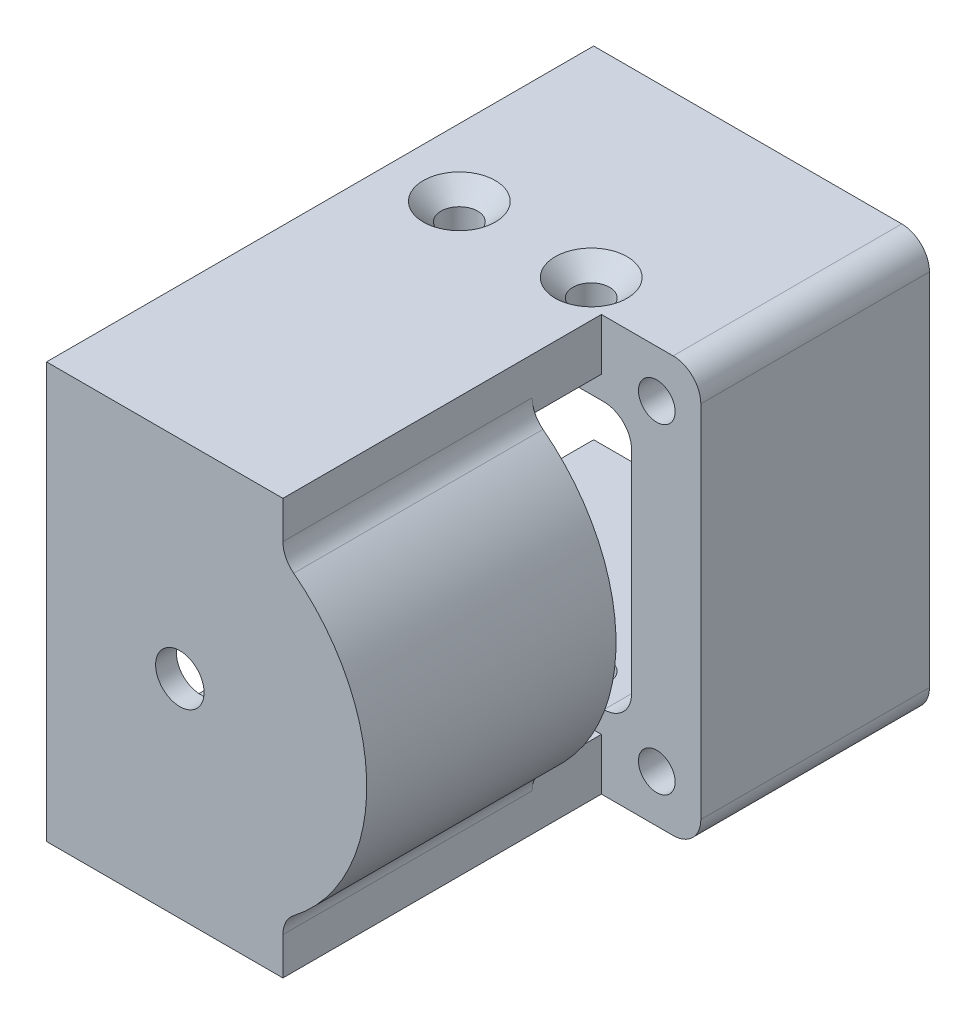
SolidWorks part; units mm, degrees
material "ABS"
ref_plane "Front Plane" through (0, 0, 0) normal (0, 0, 1) x (1, 0, 0)
ref_plane "Top Plane" through (0, 0, 0) normal (0, 1, 0) x (1, 0, 0)
ref_plane "Right Plane" through (0, 0, 0) normal (1, 0, 0) x (0, 0, -1)
sketch "Sketch1" plane through (0, 0, 0) normal (0, 0, 1) x (1, 0, 0)
  line L0 (-19.25, 19.25) -> (-19.25, 30)
  line L1 (-19.25, -19.25) -> (19.25, -19.25)
  line L3 (-19.25, 19.25) -> (19.25, 19.25)
  line L4 (19.25, -19.25) -> (19.25, 19.25)
  line L5 (-19.25, -19.25) -> (19.25, 19.25) construction
  line L6 (-19.25, 19.25) -> (19.25, -19.25) construction
  line L7 (-19.25, 30) -> (29.25, 30)
  line L8 (29.25, 30) -> (29.25, -30)
  line L9 (29.25, -30) -> (-19.25, -30)
  line L10 (-19.25, -30) -> (-19.25, -19.25)
  line L11 (0, 0) -> (19.25, 0) construction
  line L12 (19.25, 19.25) -> (29.25, 30) construction
  point P0 (0, 0)
  point P12 (22.8878, 23.1606)
  point P13 (22.8878, -23.1606)
  point P16 (24.25, 24.625)
  dimension "D1" = 38.5
  dimension "D2" = 38.5
  dimension "D3" = 60
  dimension "D4" = 10
  dimension "D5" = 2
extrude "Boss-Extrude1" add sketch "Sketch1" along normal mid plane 33.02
hole_wizard "M5 Clearance Hole1" positions "Sketch4" profile "Sketch5" hole size "M5" standard "ANSI Metric" end condition through all
sketch "Sketch4" plane through (0, 0, -16.51) normal (0, 0, -1) x (-1, 0, 0)
  point P4 (-22.8878, -23.1606)
  point P9 (-22.8878, 23.1606)
sketch "Sketch5" plane through (22.8878, -23.1606, -16.51) normal (1, 0, 0) x (0, 1, 0)
  line L0 (0, 0) -> (0, 33.02)
  line L1 (0, 33.02) -> (2.65, 33.02)
  line L2 (2.65, 33.02) -> (2.65, 0)
  line L5 (2.65, 0) -> (0, 0)
  line L11 (0, -6.35) -> (0, 107.95) construction
  dimension "Thru Hole Dia." = 5.3
  dimension "Thru Hole Depth" = 33.02
fillet "Fillet1" radius 4 4 edges at (29.25, -30, 0) (29.25, 30, 0) (19.25, -19.25, 0) (19.25, 19.25, 0)
sketch "Sketch6" plane through (0, 0, 16.51) normal (0, 0, 1) x (1, 0, 0)
  line L2 (-19.25, 22.5) -> (-19.25, 30)
  line L3 (-19.25, 30) -> (14.8878, 30)
  line L4 (25.25, 30) -> (-19.25, 30) construction
  line L5 (14.8878, 30) -> (14.8878, 22.5245)
  line L6 (22.8878, 27.7794) -> (18.8878, 25.47) construction
  line L7 (18.8878, 25.47) -> (18.8878, 20.8512) construction
  line L8 (18.8878, 20.8512) -> (22.8878, 18.5418) construction
  line L9 (22.8878, 18.5418) -> (26.8878, 20.8512) construction
  line L10 (26.8878, 20.8512) -> (26.8878, 25.47) construction
  line L11 (26.8878, 25.47) -> (22.8878, 27.7794) construction
  line L12 (0, 0) -> (19.25, 0) construction
  line L13 (19.25, 15.25) -> (19.25, -15.25) construction
  line L15 (-19.25, -22.5) -> (-19.25, -30)
  line L16 (-19.25, -30) -> (14.8878, -30)
  line L17 (14.8878, -30) -> (14.8878, -22.5245)
  line L18 (0, 22.5) -> (-19.25, 22.5)
  line L19 (0, -22.5) -> (-19.25, -22.5)
  arc A0 (0, -22.5) -> (0, 22.5) centre (0, 0) ccw
  circle A1 centre (22.8878, 23.1606) radius 4 construction
  arc A3 (14.8878, -22.5245) -> (14.8878, 22.5245) centre (0, 0) ccw
  dimension "D1" = 45
  dimension "D4" = 27
  dimension "D2" = 8
  dimension "D3" = 4
extrude "Boss-Extrude2" add sketch "Sketch6" along normal blind 43
sketch "Sketch7" plane through (29.25, 0, 0) normal (1, 0, 0) x (0, 0, -1)
  line L0 (-59.51, -22.5245) -> (-16.51, -22.5245) construction
  line L1 (-16.51, 22.5245) -> (-26.51, 22.5245)
  line L2 (-16.51, 22.5245) -> (-16.51, -22.5245)
  line L3 (-16.51, -22.5245) -> (-26.51, -22.5245)
  line L4 (-26.51, 22.5245) -> (-26.51, -22.5245)
  point P7 (0, 0)
  dimension "D1" = 10
extrude "Cut-Extrude1" cut sketch "Sketch7" against normal through all both and the other way through all
fillet "Fillet2" radius 4 2 edges at (14.8878, -22.5245, 43.01) (14.8878, 22.5245, 43.01)
sketch "Sketch8" plane through (0, 0, 59.51) normal (0, 0, 1) x (1, 0, 0)
  line L0 (-19.25, 22.5) -> (-19.25, -22.5)
  line L8 (0, -22.5) -> (-19.25, -22.5)
  line L9 (-19.25, -22.5) -> (-19.25, -30)
  line L10 (-19.25, -30) -> (14.8878, -30)
  line L11 (14.8878, -30) -> (14.8878, -24.5815)
  line L12 (14.8878, 24.5815) -> (14.8878, 30)
  line L13 (14.8878, 30) -> (-19.25, 30)
  line L14 (-19.25, 30) -> (-19.25, 22.5)
  line L15 (-19.25, 22.5) -> (0, 22.5)
  line L16 (0, -22.5) -> (-19.25, -22.5) construction
  line L17 (-19.25, -22.5) -> (-19.25, -30)
  line L18 (-19.25, -30) -> (14.8878, -30)
  line L19 (14.8878, -30) -> (14.8878, -24.5815)
  line L20 (14.8878, 24.5815) -> (14.8878, 30)
  line L21 (14.8878, 30) -> (-19.25, 30)
  line L22 (-19.25, 30) -> (-19.25, 22.5)
  line L23 (-19.25, 22.5) -> (0, 22.5) construction
  circle A0 centre (0, 0) radius 3.5
  arc A4 (0, -22.5) -> (0, 22.5) centre (0, 0) ccw
  arc A5 (16.4507, -21.4097) -> (14.8878, -24.5815) centre (18.8878, -24.5815) ccw
  arc A6 (16.4507, -21.4097) -> (16.4507, 21.4097) centre (0, 0) ccw
  arc A7 (14.8878, 24.5815) -> (16.4507, 21.4097) centre (18.8878, 24.5815) ccw
  arc A8 (0, -22.5) -> (0, 22.5) centre (0, 0) ccw construction
  arc A9 (16.4507, -21.4097) -> (14.8878, -24.5815) centre (18.8878, -24.5815) ccw
  arc A10 (16.4507, -21.4097) -> (16.4507, 21.4097) centre (0, 0) ccw
  arc A11 (14.8878, 24.5815) -> (16.4507, 21.4097) centre (18.8878, 24.5815) ccw
  dimension "D2" = 7
  dimension "D1" = 0
extrude "Boss-Extrude3" add sketch "Sketch8" along normal blind 3
sketch "Sketch9" plane through (0, 30, 0) normal (0, 1, 0) x (1, 0, 0)
  line L0 (25.25, -16.51) -> (14.8878, -16.51) construction
  line L1 (-19.05, -16.51) -> (19.05, -16.51) construction
  line L2 (-19.05, -16.51) -> (-19.05, -8.7225) construction
  line L3 (-19.05, -8.7225) -> (19.05, -8.7225) construction
  line L4 (19.05, -16.51) -> (19.05, -8.7225) construction
  line L5 (-19.05, -16.51) -> (19.05, -8.7225) construction
  line L6 (-19.05, -8.7225) -> (19.05, -16.51) construction
  line L7 (-19.25, -62.51) -> (-19.25, 16.51) construction
  line L8 (0, -12.6163) -> (0, -8.7225) construction
  point P0 (0, -12.6162)
  point P11 (-9.525, -12.6163)
  point P12 (9.525, -12.6163)
  dimension "D1" = 7.7875
  dimension "D2" = 38.1
  dimension "D3" = 0.2
  dimension "D4" = 19.05
hole_wizard "CSK for M5 Flat Head Machine Screw1" positions "Sketch10" profile "Sketch11" countersink size "M5" standard "ANSI Metric" end condition up to next
sketch "Sketch10" plane through (0, 30, 0) normal (0, 1, 0) x (1, 0, 0)
  point P0 (-9.525, -12.6163)
  point P3 (9.525, -12.6163)
sketch "Sketch11" plane through (-9.525, 30, 12.6163) normal (1, 0, 0) x (0, 0, 1)
  line L0 (0, 0) -> (0, 10.75)
  line L1 (0, 10.75) -> (2.65, 10.75)
  line L2 (2.65, 10.75) -> (2.65, 2.55)
  line L3 (2.65, 2.55) -> (5.2, 0)
  line L5 (5.2, 0) -> (0, 0)
  line L6 (-2.65, 2.55) -> (-5.2, 0) construction
  line L11 (0, -6.35) -> (0, 107.95) construction
  dimension "Thru Hole Dia." = 5.3
  dimension "Thru Hole Depth" = 10.75
  dimension "Near C'Sink Dia." = 10.4
  dimension "Near C'Sink Angle" = 90
mirror "Mirror1" about plane through (0, 0, 0) normal (0, 1, 0) of "CSK for M5 Flat Head Machine Screw1"
equation "\"D1@Boss-Extrude1\"=1.3in"
equation "\"D4@Sketch9\"=0.75in"
